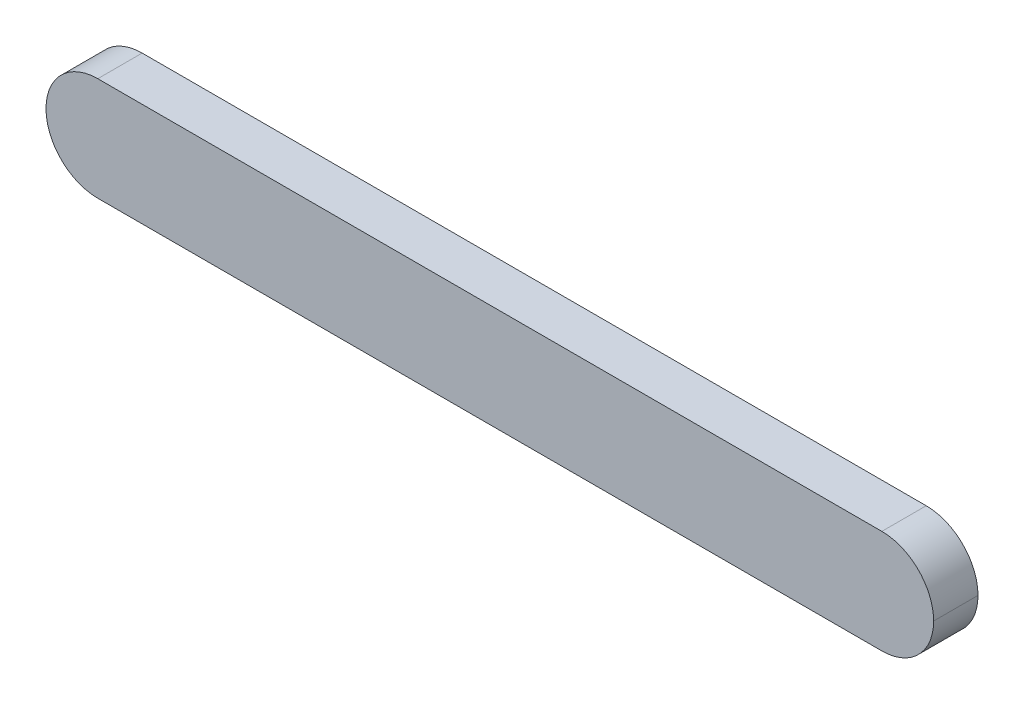
SolidWorks part; units mm, degrees
ref_plane "Front Plane" through (0, 0, 0) normal (0, 0, 1) x (1, 0, 0)
ref_plane "Top Plane" through (0, 0, 0) normal (0, 1, 0) x (1, 0, 0)
ref_plane "Right Plane" through (0, 0, 0) normal (1, 0, 0) x (0, 0, -1)
sketch "Sketch1" plane through (0, 0, 0) normal (0, 0, 1) x (1, 0, 0)
  line L1 (-30, -3.5) -> (30, -3.5)
  line L2 (-30, -3.5) -> (-30, 3.5)
  line L3 (-30, 3.5) -> (30, 3.5)
  line L4 (30, -3.5) -> (30, 3.5)
  line L5 (-30, -3.5) -> (30, 3.5) construction
  line L6 (-30, 3.5) -> (30, -3.5) construction
  point P0 (0, 0)
  dimension "D1" = 60
  dimension "D2" = 7
extrude "Boss-Extrude1" add sketch "Sketch1" along normal blind 3 contours L2 L1 L4 L3
fillet "Fillet1" radius 3.5 4 edges at (-30, -3.5, 1.5) (-30, 3.5, 1.5) (30, -3.5, 1.5) (30, 3.5, 1.5)
